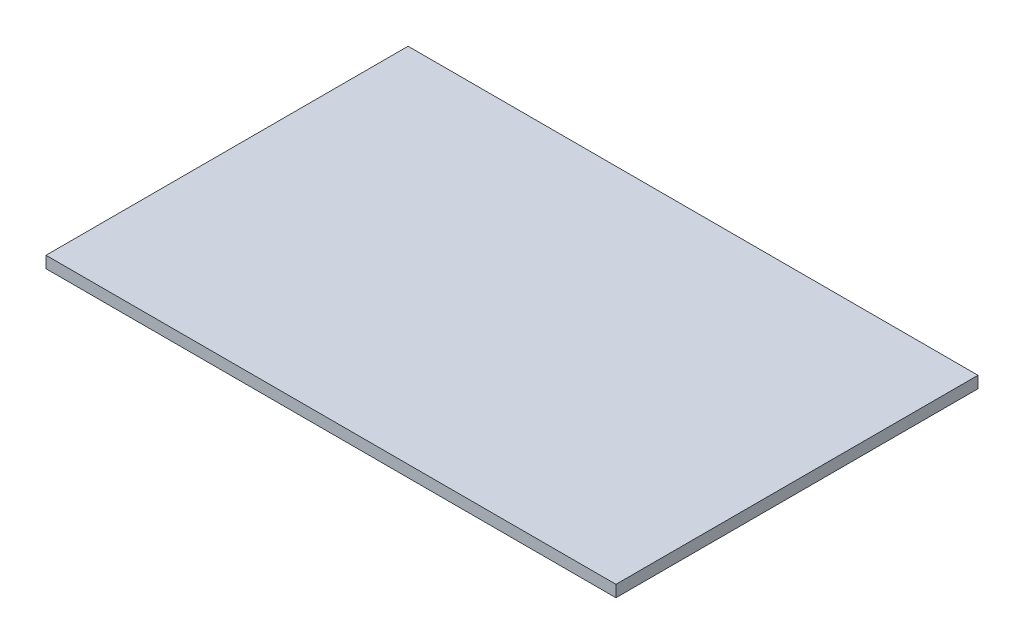
SolidWorks part; units mm, degrees
ref_plane "前视基准面" through (0, 0, 0) normal (0, 0, 1) x (1, 0, 0)
ref_plane "上视基准面" through (0, 0, 0) normal (0, 1, 0) x (1, 0, 0)
ref_plane "右视基准面" through (0, 0, 0) normal (1, 0, 0) x (0, 0, -1)
sketch "草图1" plane through (0, 0, 0) normal (0, 1, 0) x (1, 0, 0)
  line L1 (0, 0) -> (244, 0)
  line L2 (0, 0) -> (0, -155)
  line L3 (0, -155) -> (244, -155)
  line L4 (244, 0) -> (244, -155)
  dimension "D1" = 244
  dimension "D2" = 155
extrude "凸台-拉伸1" add sketch "草图1" along normal blind 5
